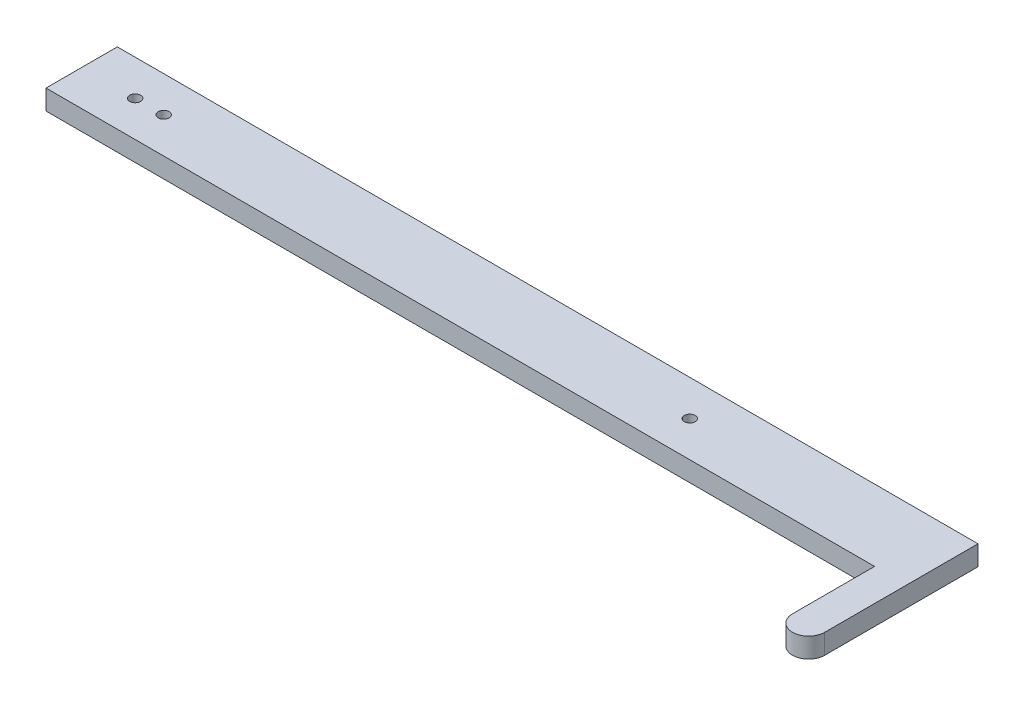
SolidWorks part; units mm, degrees
ref_plane "Front Plane" through (0, 0, 0) normal (0, 0, 1) x (1, 0, 0)
ref_plane "Top Plane" through (0, 0, 0) normal (0, 1, 0) x (1, 0, 0)
ref_plane "Right Plane" through (0, 0, 0) normal (1, 0, 0) x (0, 0, -1)
sketch "Sketch1" plane through (0, 0, 0) normal (0, 1, 0) x (1, 0, 0)
  line L1 (-167.2588, 11.5655) -> (74.0412, 11.5655)
  line L2 (-167.2588, 11.5655) -> (-167.2588, -8.4345)
  line L3 (-167.2588, -8.4345) -> (74.0412, -8.4345)
  line L4 (74.0412, 11.5655) -> (74.0412, -8.4345)
  dimension "D1" = 241.3
  dimension "D2" = 20
extrude "Boss-Extrude1" add sketch "Sketch1" along normal blind 5.588
sketch "Sketch2" plane through (0, 5.588, 0) normal (0, 1, 0) x (1, 0, 0)
  line L0 (-167.2588, 1.5655) -> (74.0412, 1.5655) construction
  line L1 (-167.2588, 11.5655) -> (-167.2588, -8.4345) construction
  line L2 (74.0412, -8.4345) -> (74.0412, 11.5655) construction
  circle A0 centre (3.2412, 1.5655) radius 1.525
  circle A1 centre (-152.2588, 1.5655) radius 1.525
  circle A2 centre (-144.2588, 1.5655) radius 1.525
  dimension "D1" = 3.05
  dimension "D2" = 70.8
  dimension "D3" = 15
  dimension "D4" = 8
extrude "Cut-Extrude1" cut sketch "Sketch2" against normal up to next
sketch "Sketch3" plane through (0, 5.588, 0) normal (0, 1, 0) x (1, 0, 0)
  line L0 (-167.2588, -8.4345) -> (74.0412, -8.4345) construction
  line L1 (65.0412, -8.4345) -> (74.0412, -8.4345)
  line L2 (65.0412, -8.4345) -> (65.0412, -31.4345)
  line L3 (65.0412, -31.4345) -> (74.0412, -31.4345)
  line L4 (74.0412, -8.4345) -> (74.0412, -31.4345)
  line L5 (74.0412, -8.4345) -> (74.0412, 11.5655) construction
  dimension "D1" = 9
  dimension "D2" = 23
extrude "Boss-Extrude2" add sketch "Sketch3" against normal up to surface (5.588 mm away) up to face at (-144.2588, 0, -0.0405)
sketch "Sketch4" plane through (0, 5.588, 0) normal (0, 1, 0) x (1, 0, 0)
  line L0 (65.0412, -31.4345) -> (74.0412, -31.4345)
  arc A0 (65.0412, -31.4345) -> (74.0412, -31.4345) centre (69.5412, -31.4345) ccw
extrude "Boss-Extrude3" add sketch "Sketch4" against normal up to surface (5.588 mm away) up to face at (-144.2588, 0, -0.0405)
